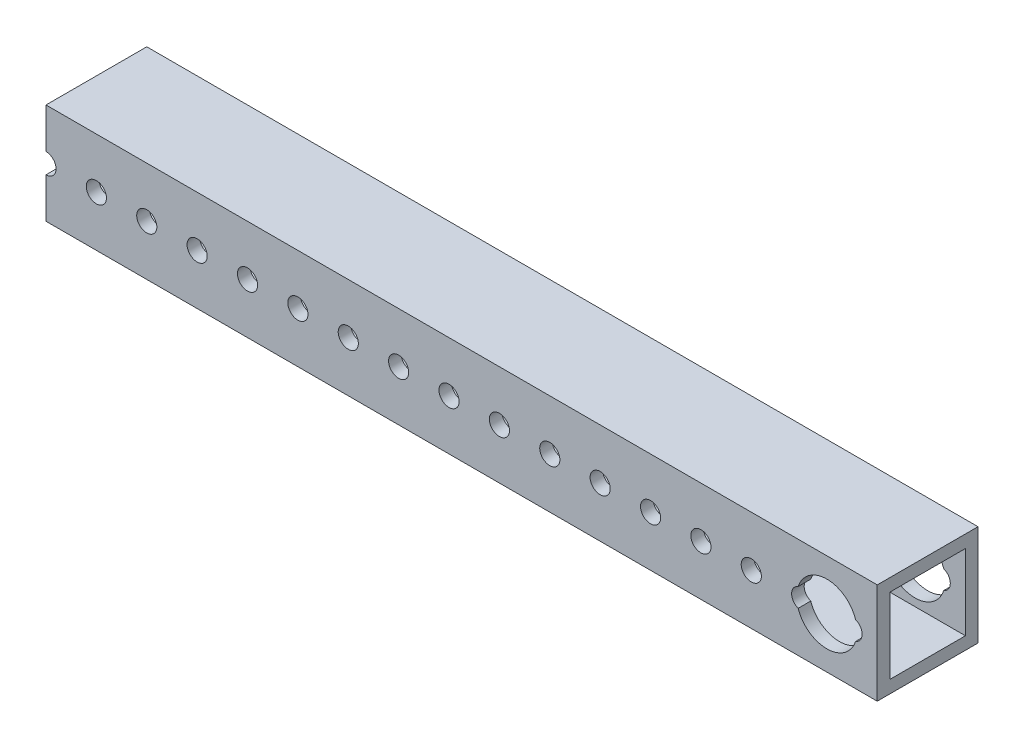
SolidWorks part; units mm, degrees
material "6061 Alloy"
ref_plane "Front Plane" through (0, 0, 0) normal (0, 0, 1) x (1, 0, 0)
ref_plane "Top Plane" through (0, 0, 0) normal (0, 1, 0) x (1, 0, 0)
ref_plane "Right Plane" through (0, 0, 0) normal (1, 0, 0) x (0, 0, -1)
sketch "Sketch1" plane through (0, 0, 0) normal (1, 0, 0) x (0, 0, -1)
  line L1 (-12.7, -12.7) -> (12.7, -12.7)
  line L2 (-12.7, -12.7) -> (-12.7, 12.7)
  line L3 (-12.7, 12.7) -> (12.7, 12.7)
  line L4 (12.7, -12.7) -> (12.7, 12.7)
  line L5 (0, 12.7) -> (0, -12.7) construction
  line L6 (-12.7, 0) -> (12.7, 0) construction
  line L7 (9.525, -9.525) -> (-9.525, -9.525)
  line L8 (9.525, -9.525) -> (9.525, 9.525)
  line L9 (9.525, 9.525) -> (-9.525, 9.525)
  line L10 (-9.525, -9.525) -> (-9.525, 9.525)
  line L11 (0, 9.525) -> (0, -9.525) construction
  line L12 (9.525, 0) -> (-9.525, 0) construction
  point P0 (0, 0)
  point P4 (0, 0)
  dimension "D1" = 25.4
  dimension "D2" = 3.175
extrude "Initial Stock" add sketch "Sketch1" along normal blind 209.55
sketch "Sketch2" plane through (0, 0, 12.7) normal (0, 0, 1) x (1, 0, 0)
  circle A0 centre (0, 0) radius 2.54
  dimension "D1" = 5.08
extrude "Initial Hole" cut sketch "Sketch2" against normal through all
pattern_linear "Hole Pattern" count 17 spacing 12.7 along (1, 0, 0) of "Initial Hole"
sketch "Sketch3" plane through (0, 0, 12.7) normal (0, 0, 1) x (1, 0, 0)
  line L0 (209.55, 12.7) -> (209.55, -12.7) construction
  line L1 (209.55, 0) -> (196.85, 0) construction
  circle A0 centre (196.85, 0) radius 7.62
  dimension "D2" = 15.24
  dimension "D1" = 12.7
extrude "Shaft Hole" cut sketch "Sketch3" against normal through all
